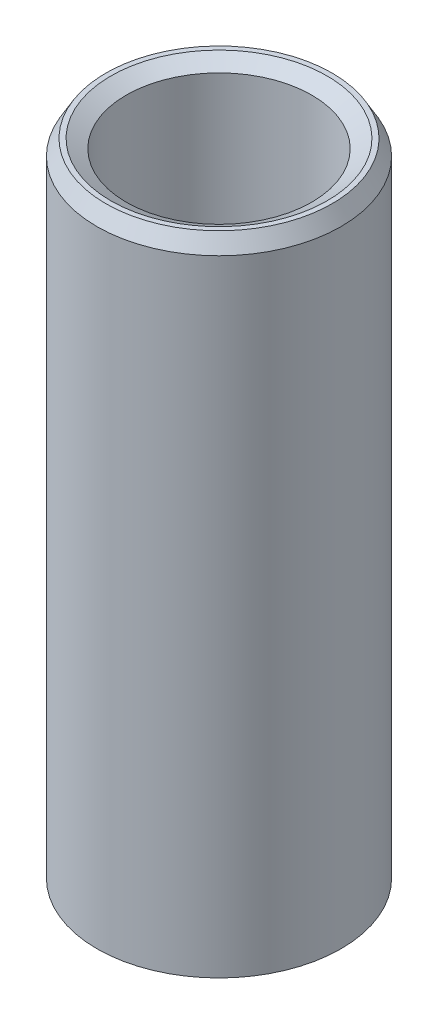
SolidWorks part; units mm, degrees
ref_plane "Front Plane" through (0, 0, 0) normal (0, 0, 1) x (1, 0, 0)
ref_plane "Top Plane" through (0, 0, 0) normal (0, 1, 0) x (1, 0, 0)
ref_plane "Right Plane" through (0, 0, 0) normal (1, 0, 0) x (0, 0, -1)
sketch "Sketch1" plane through (0, 0, 0) normal (0, 1, 0) x (1, 0, 0)
  circle A0 centre (0, 0) radius 30
  dimension "SLEEVE_OD" = 60
extrude "Boss-Extrude1" add sketch "Sketch1" along normal blind 159.6948
sketch "Sketch2" plane through (0, 0, 0) normal (0, 1, 0) x (1, 0, 0)
  circle A0 centre (0, 0) radius 22.8073
  dimension "BORE_D" = 45.6146
extrude "Cut-Extrude1" cut sketch "Sketch2" along normal through all
chamfer "Chamfer1" distance 3.78 angle 30 4 edges at (0, 159.6948, 22.8073) (0, 0, 22.8073) (0, 0, 30) (0, 159.6948, 30) first distance on face at (0, 159.6948, 22.8073) first distance on face at (0, 0, 22.8073) first distance on face at (0, 159.6948, 30)
